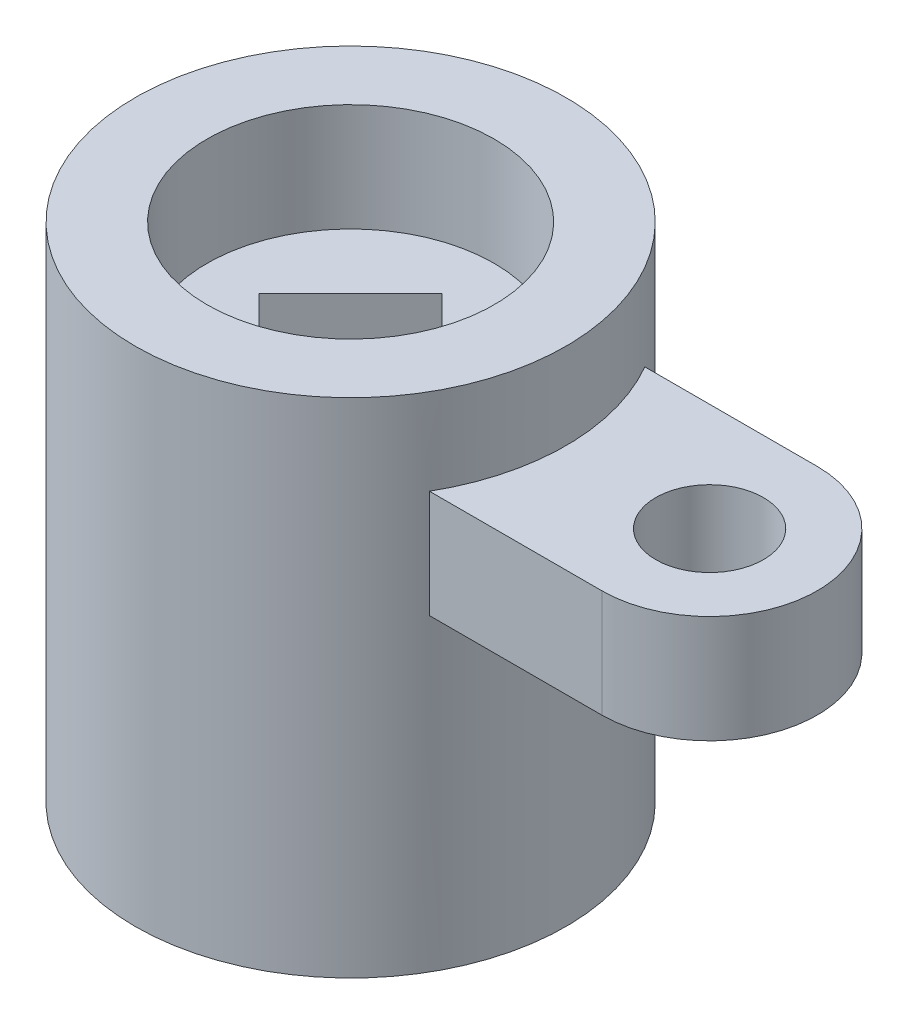
SolidWorks part; units mm, degrees
ref_plane "前视基准面" through (0, 0, 0) normal (0, 0, 1) x (1, 0, 0)
ref_plane "上视基准面" through (0, 0, 0) normal (0, 1, 0) x (1, 0, 0)
ref_plane "右视基准面" through (0, 0, 0) normal (1, 0, 0) x (0, 0, -1)
other "Configuration Table"
sketch "草图1" plane through (0, 0, 0) normal (0, 1, 0) x (1, 0, 0)
  line L0 (0, 0) -> (50, 0) construction
  line L1 (50, -15) -> (50, 15)
  line L2 (50, 15) -> (25.9808, 15)
  line L3 (50, -15) -> (25.9808, -15)
  circle A0 centre (0, 0) radius 30
  circle A1 centre (0, 0) radius 20
  arc A2 (50, -15) -> (50, 15) centre (50, 0) ccw
  circle A3 centre (50, 0) radius 7.5
  dimension "D1" = 60
  dimension "D2" = 40
  dimension "D5" = 15
  dimension "D3" = 50
  dimension "D4" = 15
extrude "凸台-拉伸1" add sketch "草图1" along normal blind 70 contours A1 A0 | A1 region at (-29.1515, 0, 0)
extrude "凸台-拉伸2" add sketch "草图1<4>" against normal blind 15 from offset 58 contours A0 L0 A3 L1 L2 | L0 A0 L3 L1 A3 | A3 L1 A2 region at (38.1127, 0, -8.4622) region at (38.1127, 0, 8.4622) region at (50.3354, 0, -11.25)
sketch "草图1<4>" plane through (0, 0, 0) normal (0, 1, 0) x (1, 0, 0) same geometry as "草图1"
sketch "草图3" plane through (0, 70, 0) normal (0, 1, 0) x (1, 0, 0)
  circle A0 centre (0, 0) radius 20
  dimension "D1" = 40
extrude "切除-拉伸1" cut sketch "草图3" against normal blind 15
sketch "草图4" plane through (0, 55, 0) normal (0, 1, 0) x (1, 0, 0)
  line L1 (0, -12.7279) -> (-12.7279, 0)
  line L2 (0, -12.7279) -> (12.7279, 0)
  line L3 (12.7279, 0) -> (0, 12.7279)
  line L4 (-12.7279, 0) -> (0, 12.7279)
  line L5 (0, -12.7279) -> (0, 12.7279) construction
  line L6 (12.7279, 0) -> (-12.7279, 0) construction
  point P0 (0, 0)
  dimension "D1" = 18
extrude "切除-拉伸2" cut sketch "草图4" against normal through all
